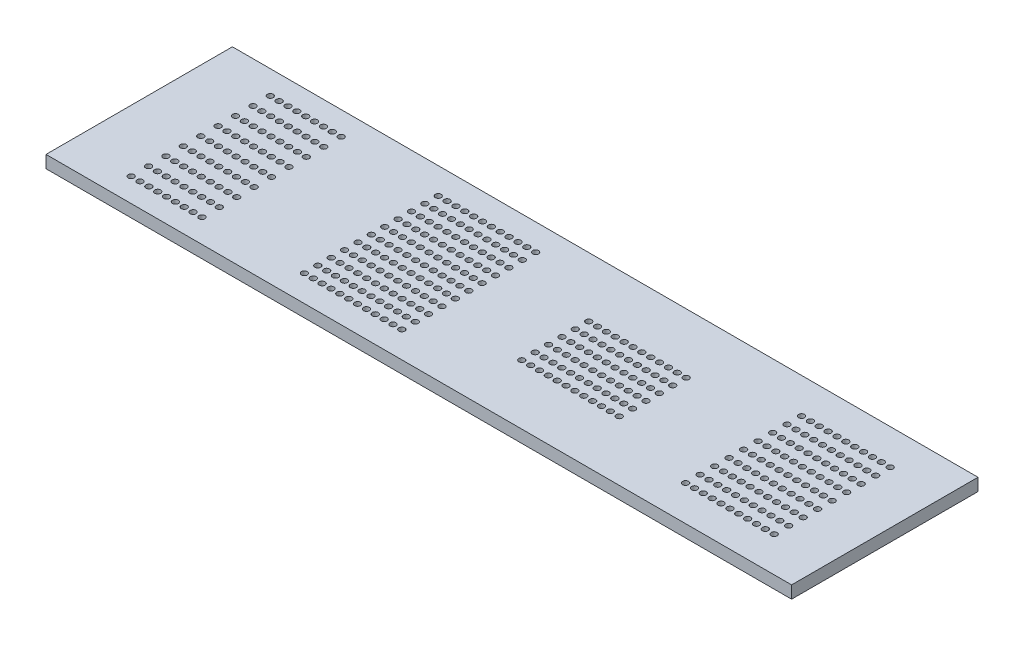
SolidWorks part; units mm, degrees
ref_plane "Plan de face" through (0, 0, 0) normal (0, 0, 1) x (1, 0, 0)
ref_plane "Plan de dessus" through (0, 0, 0) normal (0, 1, 0) x (1, 0, 0)
ref_plane "Plan de droite" through (0, 0, 0) normal (1, 0, 0) x (0, 0, -1)
sketch "Esquisse2" plane through (0, 0, 0) normal (0, 1, 0) x (1, 0, 0)
  line L1 (-60, -15) -> (60, -15)
  line L2 (-60, -15) -> (-60, 15)
  line L3 (-60, 15) -> (60, 15)
  line L4 (60, -15) -> (60, 15)
  line L5 (-60, -15) -> (60, 15) construction
  line L6 (-60, 15) -> (60, -15) construction
  point P0 (0, 0)
  dimension "D1" = 30
  dimension "D2" = 120
extrude "Boss.-Extru.1" add sketch "Esquisse2" along normal blind 2 contours L3 L4 L1 L2
sketch "Cavités" plane through (0, 0, 0) normal (0, 1, 0) x (1, 0, 0)
  line L0 (-60, -15) -> (60, -15) construction
  line L1 (-58.4, 15) -> (-30.4, 15) construction
  line L2 (-58.4, 15) -> (-58.4, -15) construction
  line L3 (-58.4, -15) -> (-30.4, -15) construction
  line L4 (-30.4, 15) -> (-30.4, -15) construction
  line L5 (-60, 15) -> (60, 15) construction
  line L6 (-28.8, 15) -> (-0.8, 15) construction
  line L7 (-28.8, 15) -> (-28.8, -15) construction
  line L8 (-28.8, -15) -> (-0.8, -15) construction
  line L9 (-0.8, 15) -> (-0.8, -15) construction
  line L10 (-30.4, 15) -> (-28.8, 15) construction
  line L11 (0.8, 15) -> (28.8, 15) construction
  line L12 (0.8, 15) -> (0.8, -15) construction
  line L13 (0.8, -15) -> (28.8, -15) construction
  line L14 (28.8, 15) -> (28.8, -15) construction
  line L15 (30.4, 15) -> (58.4, 15) construction
  line L16 (30.4, 15) -> (30.4, -15) construction
  line L17 (30.4, -15) -> (58.4, -15) construction
  line L18 (58.4, 15) -> (58.4, -15) construction
  line L19 (-0.8, 15) -> (0.8, 15) construction
  line L20 (28.8, 15) -> (30.4, 15) construction
  line L21 (-60, 15) -> (-58.4, 15) construction
  line L22 (58.4, 15) -> (60, 15) construction
  dimension "D1" = 28
  dimension "D2" = 1.6
sketch "Esquisse7" plane through (0, 2, 0) normal (0, 1, 0) x (1, 0, 0)
  line L0 (-58.4, 0) -> (-50.096, 0) construction
  line L1 (-50.096, 11.2) -> (-38.704, 11.2) construction
  line L2 (-50.096, 11.2) -> (-50.096, -11.2) construction
  line L3 (-50.096, -11.2) -> (-38.704, -11.2) construction
  line L4 (-38.704, 11.2) -> (-38.704, -11.2) construction
  line L5 (-58.4, 15) -> (-58.4, -15) construction
  line L6 (-38.704, 0) -> (-30.4, 0) construction
  line L7 (-30.4, 15) -> (-30.4, -15) construction
  dimension "D1" = 11.392
  dimension "D2" = 22.4
sketch "Esquisse8" plane through (0, 2, 0) normal (0, 1, 0) x (1, 0, 0)
  circle A0 centre (-50.096, 11.2) radius 0.475
  dimension "D1" = 0.95
extrude "Enlèv. mat.-Extru.3" cut sketch "Esquisse8" against normal up to next
pattern_linear "Répétition linéaire4" count 9 spacing 1.424 along (1, 0, 0) count 9 spacing 2.8 along (0, 0, 1) of "Enlèv. mat.-Extru.3"
sketch "Esquisse9" plane through (0, 2, 0) normal (0, 1, 0) x (1, 0, 0)
  line L0 (-28.8, 0) -> (-22.6375, 0) construction
  line L1 (-22.6375, 10.77) -> (-6.9625, 10.77) construction
  line L2 (-22.6375, 10.77) -> (-22.6375, -10.77) construction
  line L3 (-22.6375, -10.77) -> (-6.9625, -10.77) construction
  line L4 (-6.9625, 10.77) -> (-6.9625, -10.77) construction
  line L5 (-28.8, 15) -> (-28.8, -15) construction
  line L6 (-6.9625, 0) -> (-0.8, 0) construction
  line L7 (-0.8, 15) -> (-0.8, -15) construction
  dimension "D1" = 15.675
  dimension "D2" = 21.54
sketch "Esquisse10" plane through (0, 2, 0) normal (0, 1, 0) x (1, 0, 0)
  circle A0 centre (-22.6375, 10.77) radius 0.475
  dimension "D1" = 0.95
extrude "Enlèv. mat.-Extru.4" cut sketch "Esquisse10" against normal up to next
pattern_linear "Répétition linéaire5" count 12 spacing 1.425 along (1, 0, 0) count 11 spacing 2.154 along (0, 0, 1) of "Enlèv. mat.-Extru.4"
sketch "Esquisse11" plane through (0, 2, 0) normal (0, 1, 0) x (1, 0, 0)
  line L0 (0.8, 0) -> (6.9625, 0) construction
  line L1 (6.9625, 5.385) -> (22.6375, 5.385) construction
  line L2 (6.9625, 5.385) -> (6.9625, -5.385) construction
  line L3 (6.9625, -5.385) -> (22.6375, -5.385) construction
  line L4 (22.6375, 5.385) -> (22.6375, -5.385) construction
  line L5 (0.8, 15) -> (0.8, -15) construction
  line L6 (22.6375, 0) -> (28.8, 0) construction
  line L7 (28.8, 15) -> (28.8, -15) construction
  dimension "D1" = 15.675
  dimension "D2" = 10.77
sketch "Esquisse12" plane through (0, 2, 0) normal (0, 1, 0) x (1, 0, 0)
  circle A0 centre (6.9625, 5.385) radius 0.475
  dimension "D1" = 0.95
extrude "Enlèv. mat.-Extru.5" cut sketch "Esquisse12" against normal up to next
pattern_linear "Répétition linéaire6" count 12 spacing 1.425 along (1, 0, 0) count 6 spacing 2.154 along (0, 0, 1) of "Enlèv. mat.-Extru.5"
sketch "Esquisse13" plane through (0, 2, 0) normal (0, 1, 0) x (1, 0, 0)
  line L0 (30.4, 0) -> (37.275, 0) construction
  line L1 (37.275, 9.332) -> (51.525, 9.332) construction
  line L2 (37.275, 9.332) -> (37.275, -9.332) construction
  line L3 (37.275, -9.332) -> (51.525, -9.332) construction
  line L4 (51.525, 9.332) -> (51.525, -9.332) construction
  line L5 (30.4, 15) -> (30.4, -15) construction
  line L6 (51.525, 0) -> (58.4, 0) construction
  line L7 (58.4, 15) -> (58.4, -15) construction
  dimension "D1" = 18.664
  dimension "D2" = 14.25
sketch "Esquisse14" plane through (0, 2, 0) normal (0, 1, 0) x (1, 0, 0)
  circle A0 centre (37.275, 9.332) radius 0.475
  dimension "D1" = 0.95
extrude "Enlèv. mat.-Extru.6" cut sketch "Esquisse14" against normal up to next
pattern_linear "Répétition linéaire7" count 11 spacing 1.425 along (1, 0, 0) count 9 spacing 2.333 along (0, 0, 1) of "Enlèv. mat.-Extru.6"
